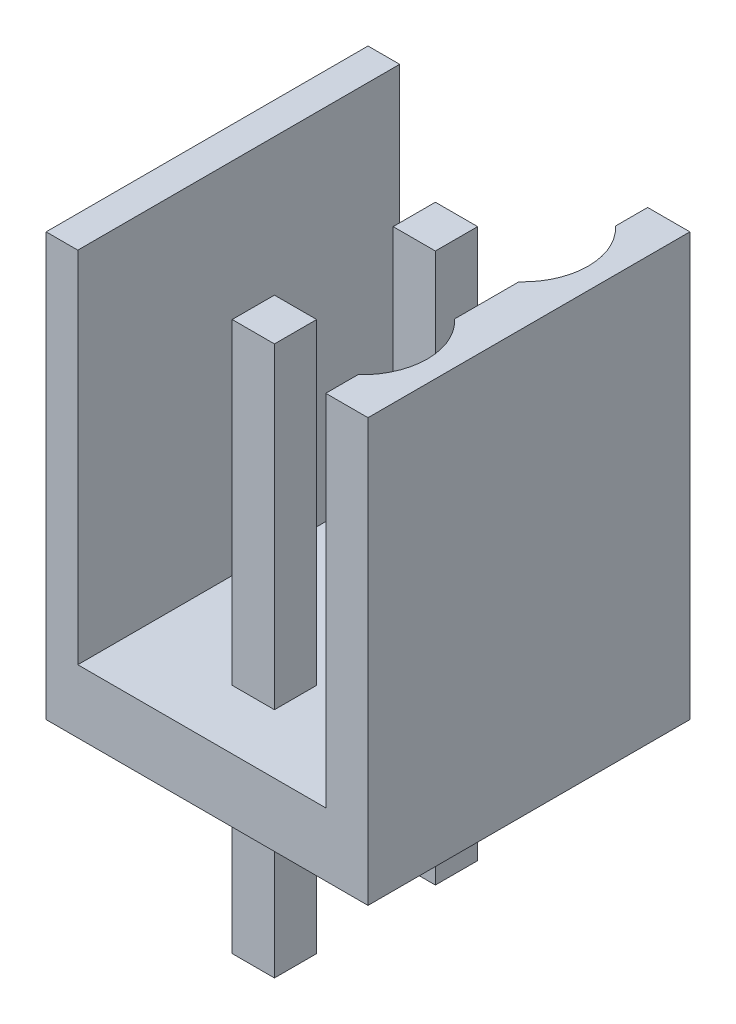
SolidWorks part; units mm, degrees
ref_plane "前视基准面" through (0, 0, 0) normal (0, 0, 1) x (1, 0, 0)
ref_plane "上视基准面" through (0, 0, 0) normal (0, 1, 0) x (1, 0, 0)
ref_plane "右视基准面" through (0, 0, 0) normal (1, 0, 0) x (0, 0, -1)
sketch "草图1" plane through (0, 0, 0) normal (0, 1, 0) x (1, 0, 0)
  line L0 (0, 11.3571) -> (0, -8.6742) construction
  line L1 (-3.81, 3.81) -> (3.81, 3.81)
  line L2 (-3.81, 3.81) -> (-3.81, -3.81)
  line L3 (-3.81, -3.81) -> (3.81, -3.81)
  line L4 (3.81, 3.81) -> (3.81, -3.81)
  line L5 (-11.8577, 0) -> (16.1453, 0) construction
  dimension "D1" = 7.62
  dimension "D2" = 7.62
extrude "拉伸1" add sketch "草图1" along normal blind 10
sketch "草图2" plane through (0, 10, 0) normal (0, 1, 0) x (-1, 0, 0)
  line L0 (-4.9146, 0) -> (4.5942, 0) construction
  line L1 (-1.7494, -1.905) -> (-4.2075, -1.905) construction
  line L2 (-2.81, -3.81) -> (-2.81, -3.0498)
  line L3 (-3.81, -3.81) -> (3.81, -3.81) construction
  line L4 (-3.81, 3.81) -> (-3.81, -3.81) construction
  line L5 (-3.31, -1.905) -> (-3.31, -3.9781) construction
  line L6 (-2.81, -3.81) -> (3.06, -3.81)
  line L7 (3.06, -3.81) -> (3.06, 3.81)
  line L8 (-2.81, -0.7602) -> (-2.81, 0.7602)
  line L9 (3.81, -3.81) -> (3.81, 3.81) construction
  line L10 (-2.81, 3.81) -> (3.06, 3.81)
  line L11 (-2.81, 3.81) -> (-2.81, 3.0498)
  arc A0 (-2.81, 0.7602) -> (-2.81, 3.0498) centre (-1.7494, 1.905) cw
  arc A1 (-2.81, -0.7602) -> (-2.81, -3.0498) centre (-1.7494, -1.905) ccw
  point P16 (-2.81, 0)
  point P25 (3.06, 0)
  dimension "D1" = 1.905
  dimension "D2" = 1.5606
  dimension "D4" = 0.5
  dimension "D3" = 1
  dimension "D5" = 0.75
extrude "切除-拉伸1" cut sketch "草图2" against normal offset from surface (8.5 mm away) 1.5 up to face at (0, 0, 0)
sketch "草图3" plane through (0, 0, 0) normal (0, -1, 0) x (1, 0, 0)
  line L0 (4.5117, 0) -> (-4.6667, 0) construction
  line L1 (2.1187, 1.905) -> (-2.5308, 1.905) construction
  line L2 (0.19, 2.405) -> (-0.81, 2.405)
  line L3 (0.19, 2.405) -> (0.19, 1.405)
  line L4 (0.19, 1.405) -> (-0.81, 1.405)
  line L5 (-0.81, 2.405) -> (-0.81, 1.405)
  line L6 (-0.31, 3.5474) -> (-0.31, 0.8266) construction
  line L7 (-3.81, -3.81) -> (-3.81, 3.81) construction
  line L8 (-0.81, -2.405) -> (-0.81, -1.405)
  line L9 (0.19, -1.405) -> (-0.81, -1.405)
  line L10 (0.19, -2.405) -> (0.19, -1.405)
  line L11 (0.19, -2.405) -> (-0.81, -2.405)
  dimension "D1" = 1
  dimension "D2" = 1
  dimension "D3" = 1.905
  dimension "D4" = 3.5
extrude "拉伸2" add sketch "草图3" along normal blind 4 and the other way offset from surface 1 other way up to face at (-3.435, 10, 0)
